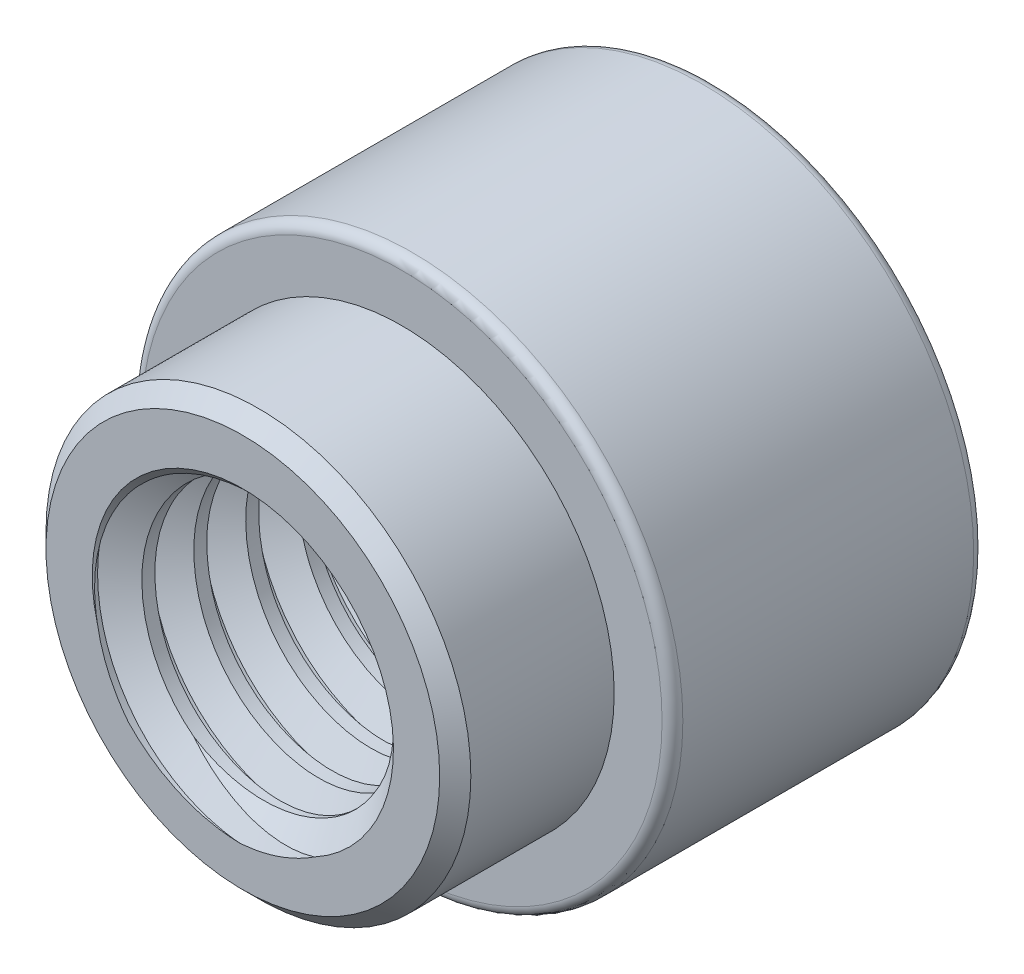
SolidWorks part; units mm, degrees
ref_plane "Ebene vorne" through (0, 0, 0) normal (0, 0, 1) x (1, 0, 0)
ref_plane "Ebene oben" through (0, 0, 0) normal (0, 1, 0) x (1, 0, 0)
ref_plane "Ebene rechts" through (0, 0, 0) normal (1, 0, 0) x (0, 0, -1)
sketch "Skizze1" plane through (0, 0, 0) normal (1, 0, 0) x (0, 0, -1)
  line L0 (-1.38, 2.045) -> (-1.53, 1.895)
  line L1 (0, 1.25) -> (-1.53, 1.25)
  line L2 (-1.53, 1.895) -> (-1.53, 1.25)
  line L3 (-1.38, 2.045) -> (0, 2.045)
  line L4 (0, 2.045) -> (0, 2.5058)
  line L5 (0.1, 2.6058) -> (2.9, 2.6058)
  line L6 (3, 2.5058) -> (3, 1.25)
  line L7 (3, 1.25) -> (0, 1.25)
  line L8 (-1.53, 0) -> (3, 0)
  arc A0 (0, 2.5058) -> (0.1, 2.6058) centre (0.1, 2.5058) cw
  arc A1 (2.9, 2.6058) -> (3, 2.5058) centre (2.9, 2.5058) cw
  point P5 (-1.53, 2.045)
  point P10 (0, 2.6058)
  point P13 (3, 2.6058)
  dimension "D5" = 0.1
  dimension "D1" = 1.25
  dimension "D2" = 2.045
  dimension "D3" = 1.53
  dimension "D4" = 3
revolve "Rotation1" add sketch "Skizze1" angle 360 about L8 region at (0, 1.8625, -0.9834)
thread "Gewinde1" pitch 0.5 method cut profile "Gewindeprofil1" start angle 0, offset 1, length 0, pitch 0.5, diameter 2.5
ref_plane "Ebene1" through (1.25, 0, -4) normal (0, -1, 0) x (1, 0, 0)
sketch "Gewindeprofil1" plane through (1.25, 0, -4) normal (0, -1, 0) x (1, 0, 0)
  line L0 (0, 0) -> (0, 0.5) construction
  line L1 (0, 0) -> (0.2706, 0.1562)
  line L2 (0.2706, 0.1562) -> (0.2706, 0.2187)
  line L3 (0.2706, 0.2187) -> (0, 0.375)
  line L4 (0.2706, 0.1875) -> (0, 0.1875) construction
  line L11 (0, 0) -> (0, 0.375)
  point P2 (0, 0)
  dimension "Pitch" = 0.5
  dimension "Profile_Angle" = 60
  dimension "Profile_Land" = 0.0625
  dimension "Profile_Height" = 0.2706
sketch "Skizze4" plane through (0, 0, 0) normal (1, 0, 0) x (0, 0, -1)
  line L0 (-1.53, 1.25) -> (-1.33, 1.25)
  line L1 (0, 1.25) -> (-1.53, 1.25) construction
  line L2 (-1.53, 1.25) -> (-1.53, 1.45)
  line L3 (-1.53, 1.45) -> (-1.33, 1.25)
  line L4 (3, 1.25) -> (2.8, 1.25)
  line L5 (2.8, 1.25) -> (3, 1.45)
  line L6 (3, 2.5058) -> (3, 1.25) construction
  line L7 (3, 1.45) -> (3, 1.25)
  line L8 (-1.53, 0) -> (3, 0)
revolve "Schnitt-Rotation1" cut sketch "Skizze4" angle 360 about L8 region at (0, 1.3167, 1.4633) region at (0, 1.3167, -2.9333)
